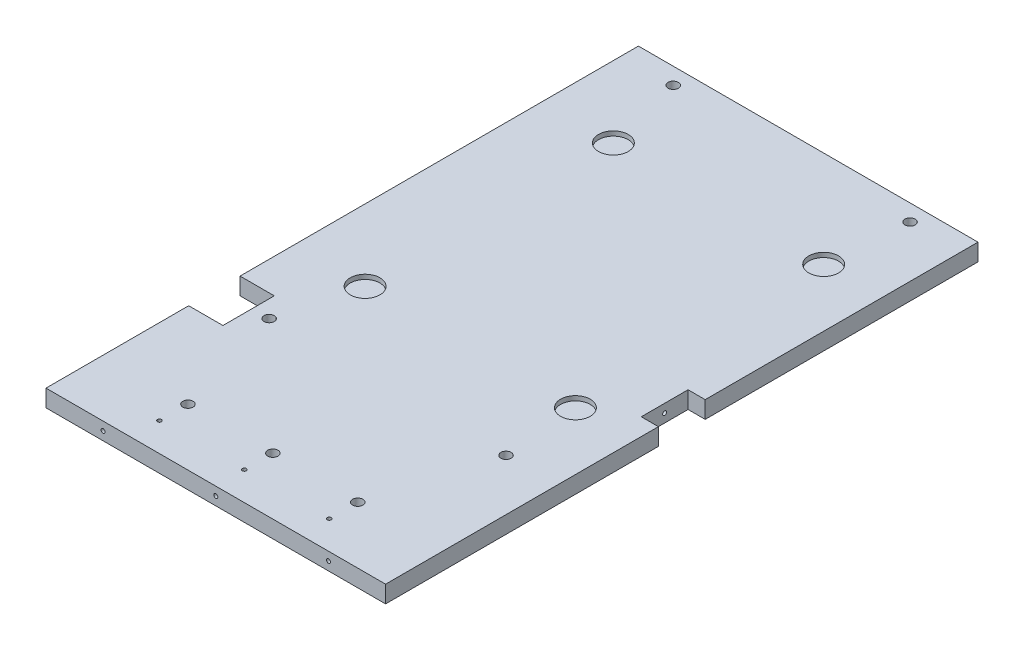
SolidWorks part; units mm, degrees
ref_plane "前视基准面" through (0, 0, 0) normal (0, 0, 1) x (1, 0, 0)
ref_plane "上视基准面" through (0, 0, 0) normal (0, 1, 0) x (1, 0, 0)
ref_plane "右视基准面" through (0, 0, 0) normal (1, 0, 0) x (0, 0, -1)
other "Configuration Table"
sketch "草图1" plane through (0, 0, 0) normal (0, 1, 0) x (1, 0, 0)
  line L1 (-29.75, -51.9) -> (29.75, -51.9)
  line L2 (-29.75, -51.9) -> (-29.75, 51.9)
  line L3 (-29.75, 51.9) -> (29.75, 51.9)
  line L4 (29.75, -51.9) -> (29.75, 51.9)
  line L5 (-29.75, -51.9) -> (29.75, 51.9) construction
  line L6 (-29.75, 51.9) -> (29.75, -51.9) construction
  point P0 (0, 0)
  dimension "D1" = 59.5
  dimension "D5" = 103.8
extrude "凸台-拉伸1" add sketch "草图1" along normal blind 3 contours L3 L4 L1 L2
sketch "草图2" plane through (0, 3, 0) normal (0, 1, 0) x (1, 0, 0)
  line L0 (-29.75, 51.9) -> (29.75, 51.9) construction
  line L1 (29.75, -51.9) -> (29.75, 51.9) construction
  line L7 (19.6129, 35) -> (19.6129, -8.5) construction
  circle A0 centre (19.6129, 35) radius 2.6
  circle A1 centre (19.6129, -8.5) radius 2.6
  circle A2 centre (-17.24, -8.5) radius 2.6
  circle A3 centre (-17.24, 35) radius 2.6
  dimension "D3" = 5.2
  dimension "D1" = 16.9
  dimension "D2" = 10.1371
  dimension "D4" = 36.8529
  dimension "D5" = 43.5
extrude "切除-拉伸1" cut sketch "草图2" against normal blind 0.8
sketch "草图3" plane through (29.75, 0, 0) normal (1, 0, 0) x (0, 0, -1)
  line L0 (-51.9, 3) -> (51.9, 3) construction
  line L1 (-4.1, 3) -> (4.1, 3)
  line L2 (-4.1, 3) -> (-4.1, 0)
  line L3 (-4.1, 0) -> (4.1, 0)
  line L4 (4.1, 3) -> (4.1, 0)
  line L5 (-51.9, 0) -> (51.9, 0) construction
  circle A0 centre (0, 1.5) radius 0.35
  point P11 (0, 0)
  point P12 (-4.1, 1.5)
  dimension "D2" = 0.7
  dimension "D1" = 8.2
extrude "切除-拉伸2" cut sketch "草图3" against normal blind 3 contours L3 L4 L1 L2
extrude "切除-拉伸4" cut sketch "草图3<3>" against normal blind 3 from surface contours A0 starting at face at (26.75, 1.5, 0)
sketch "草图3<3>" plane through (29.75, 0, 0) normal (1, 0, 0) x (0, 0, -1) same geometry as "草图3"
sketch "草图4" plane through (0, 0, -51.9) normal (0, 0, -1) x (-1, 0, 0)
  line L0 (-29.75, 3) -> (-29.75, 0) construction
  line L1 (-29.75, 1.5) -> (-19.75, 1.5) construction
  line L2 (-19.75, 1.5) -> (0, 1.5) construction
  line L3 (0, 1.5) -> (19.75, 1.5) construction
  line L4 (19.75, 1.5) -> (29.75, 1.5) construction
  line L5 (29.75, 3) -> (29.75, 0) construction
  circle A0 centre (-19.75, 1.5) radius 0.35
  circle A1 centre (0, 1.5) radius 0.35
  circle A2 centre (19.75, 1.5) radius 0.35
  dimension "D1" = 0.7
  dimension "D2" = 10
sketch "草图5" plane through (-29.75, 0, 0) normal (-1, 0, 0) x (0, 0, 1)
  line L0 (0, 0) -> (0, 3) construction
  line L1 (51.9, 0) -> (-51.9, 0) construction
  line L2 (51.9, 3) -> (-51.9, 3) construction
  line L3 (-34.6, 1.5) -> (-51.9, 1.5) construction
  line L4 (-34.6, 1.5) -> (-17.3, 1.5) construction
  line L5 (-17.3, 1.5) -> (0, 1.5) construction
  line L6 (-51.9, 1.85) -> (-51.9, 1.15) construction
  circle A0 centre (-34.6, 1.5) radius 0.35
  circle A1 centre (-17.3, 1.5) radius 0.35
  dimension "D1" = 0.7
extrude "切除-拉伸5" cut sketch "草图4" against normal blind 3
extrude "切除-拉伸6" cut sketch "草图5" against normal blind 3
mirror "镜向1" about plane through (0, 0, 0) normal (0, 0, 1) of "切除-拉伸5", "切除-拉伸6"
sketch "草图8" plane through (0, 3, 0) normal (0, 1, 0) x (1, 0, 0)
  line L0 (-29.75, -51.9) -> (-29.75, 51.9) construction
  line L1 (-29.75, -26.9) -> (-23.75, -26.9)
  line L2 (-29.75, -26.9) -> (-29.75, -17.9)
  line L3 (-29.75, -17.9) -> (-23.75, -17.9)
  line L4 (-23.75, -26.9) -> (-23.75, -17.9)
  line L5 (-29.75, -51.9) -> (29.75, -51.9) construction
  dimension "D1" = 25
  dimension "D2" = 9
  dimension "D3" = 6
extrude "切除-拉伸7" cut sketch "草图8" against normal through all
sketch "草图9" plane through (0, 3, 0) normal (0, 1, 0) x (1, 0, 0)
  line L0 (29.75, 4.1) -> (29.75, 51.9) construction
  line L1 (-29.75, -17.9) -> (-29.75, 51.9) construction
  line L2 (-29.75, 51.9) -> (29.75, 51.9) construction
  line L4 (-29.75, -51.9) -> (29.75, -51.9) construction
  circle A0 centre (-20.75, 49) radius 0.9
  circle A1 centre (20.75, 49) radius 0.9
  circle A2 centre (-20.75, -21.8) radius 0.9
  circle A3 centre (20.75, -21.8) radius 0.9
  dimension "D3" = 1.8
  dimension "D1" = 9
  dimension "D2" = 9
  dimension "D4" = 2.9
  dimension "D6" = 30.1
extrude "切除-拉伸8" cut sketch "草图9" against normal through all
sketch "草图10" plane through (0, 3, 0) normal (0, 1, 0) x (1, 0, 0)
  line L0 (29.75, -41.9) -> (14.875, -41.9) construction
  line L1 (29.75, -51.9) -> (29.75, -4.1) construction
  line L2 (14.875, -41.9) -> (0, -41.9) construction
  line L3 (0, -41.9) -> (-14.875, -41.9) construction
  line L4 (-14.875, -41.9) -> (-29.75, -41.9) construction
  line L5 (-29.75, -51.9) -> (-29.75, -26.9) construction
  line L6 (-29.75, -51.9) -> (29.75, -51.9) construction
  circle A0 centre (14.875, -46.9) radius 0.35
  circle A1 centre (-14.875, -46.9) radius 0.35
  circle A2 centre (14.875, -41.9) radius 0.9
  circle A3 centre (-14.875, -41.9) radius 0.9
  circle A4 centre (0, -46.9) radius 0.35
  circle A5 centre (0, -41.9) radius 0.9
  point P20 (0, 0)
  point P21 (0, 0)
  point P22 (0, 0)
  point P23 (14.875, -45.9419)
  point P24 (0, -45.9419)
  point P25 (-14.875, -46.3665)
  dimension "D1" = 1.8
  dimension "D2" = 0.7
  dimension "D3" = 10
  dimension "D4" = 5
extrude "切除-拉伸9" cut sketch "草图10" against normal through all
